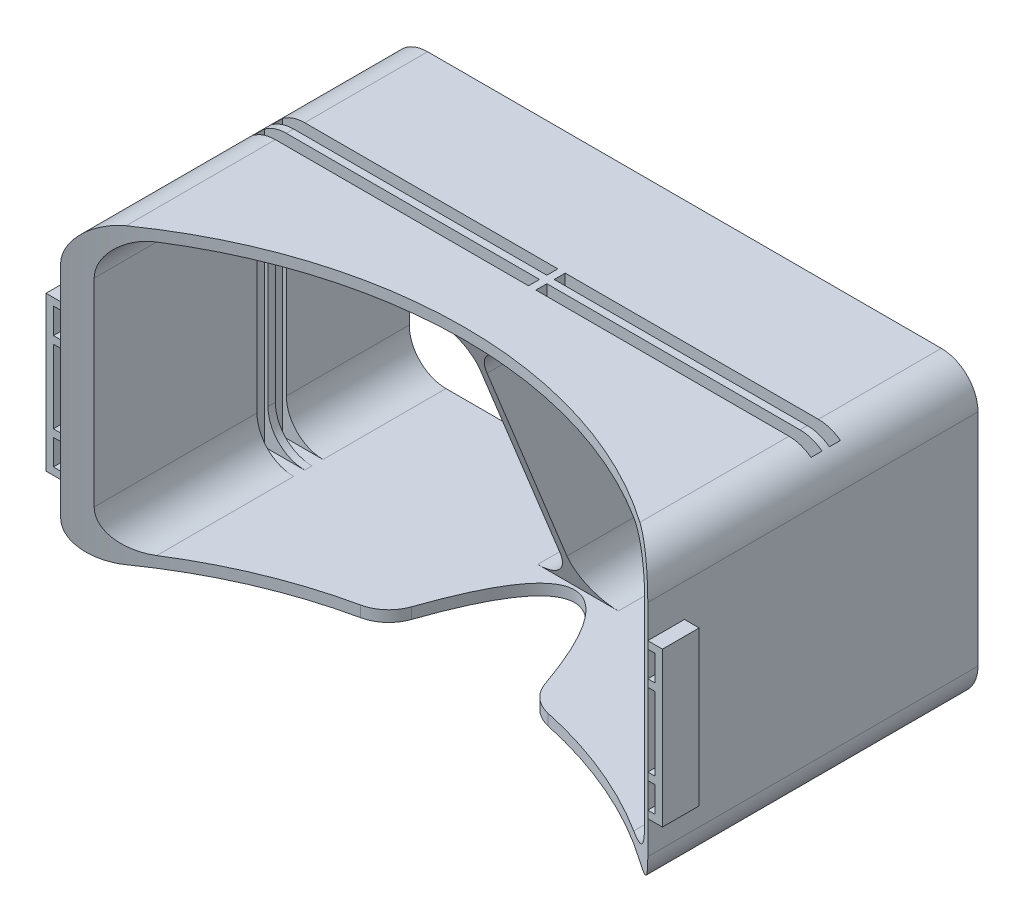
SolidWorks part; units mm, degrees
ref_plane "Plano frontal" through (0, 0, 0) normal (0, 0, 1) x (1, 0, 0)
ref_plane "Plano superior" through (0, 0, 0) normal (0, 1, 0) x (1, 0, 0)
ref_plane "Plano direito" through (0, 0, 0) normal (1, 0, 0) x (0, 0, -1)
sketch "Esboço1" plane through (0, 0, 0) normal (0, 0, 1) x (1, 0, 0)
  line L1 (-86.9655, 43.3333) -> (73.0345, 43.3333)
  line L2 (-86.9655, 43.3333) -> (-86.9655, -36.6667)
  line L3 (-86.9655, -36.6667) -> (73.0345, -36.6667)
  line L4 (73.0345, 43.3333) -> (73.0345, -36.6667)
  dimension "D1" = 160
  dimension "D2" = 80
extrude "Ressalto-extrusão1" add sketch "Esboço1" along normal blind 90
sketch "Esboço2" plane through (0, 0, 90) normal (0, 0, 1) x (1, 0, 0)
  line L0 (-86.9655, 43.3333) -> (-86.9655, -36.6667) construction
  line L1 (-81.9655, 40.3333) -> (68.0345, 40.3333)
  line L2 (-81.9655, 40.3333) -> (-81.9655, -33.6667)
  line L3 (-81.9655, -33.6667) -> (68.0345, -33.6667)
  line L4 (68.0345, 40.3333) -> (68.0345, -33.6667)
  line L5 (73.0345, -36.6667) -> (73.0345, 43.3333) construction
  line L6 (-86.9655, -36.6667) -> (73.0345, -36.6667) construction
  dimension "D1" = 3
  dimension "D2" = 5
  dimension "D3" = 5
  dimension "D4" = 3
extrude "Corte-extrusão1" cut sketch "Esboço2" against normal blind 90
sketch "Esboço3" plane through (0, 43.3333, 0) normal (0, 1, 0) x (1, 0, 0)
  line L0 (-86.9655, -90) -> (73.0345, -90)
  line L1 (-6.9655, -90) -> (-6.9655, -60)
  arc A0 (-86.9655, -90) -> (73.0345, -90) centre (-6.9655, -181.6667) cw
  line M3 (-86.9655, -90) -> (73.0345, -90)
  dimension "D1" = 30
extrude "Corte-extrusão2" cut sketch "Esboço3" against normal blind 90 contours A0 L1 L0 | A0 L1 M3
sketch "Esboço4" plane through (0, -36.6667, 0) normal (0, -1, 0) x (1, 0, 0)
  line L0 (-86.9655, 30) -> (73.0345, 30)
  line L1 (-86.9655, 90) -> (-86.9655, 0) construction
  line L2 (73.0345, 90) -> (73.0345, 0) construction
  line L3 (-6.9655, 60) -> (-86.9655, 60)
  line L4 (-6.9655, 60) -> (-6.9655, 30)
  line L5 (-26.9655, 61.6551) -> (-26.9655, 30)
  line L6 (13.0345, 61.6551) -> (13.0345, 30)
  arc A0 (-86.9655, 90) -> (73.0345, 90) centre (-6.9655, 181.6667) ccw construction
  dimension "D1" = 60
  dimension "D2" = 60
  dimension "D3" = 60
  dimension "D4" = 60
sketch "Esboço5" plane through (0, -36.6667, 0) normal (0, -1, 0) x (1, 0, 0)
  spline S0 degree 2 poles (-26.9655, 61.6551) (-6.9655, -1.6551) (13.0345, 61.6551) knots 0 0 0 1 1 1
extrude "Corte-extrusão3" cut sketch "Esboço5" along normal through all from surface at -3
fillet "Filete1" radius 10 2 edges at (-26.9655, -35.1667, 61.6551)
fillet "Filete2" radius 10 2 edges at (13.0345, -35.1667, 61.6551)
ref_plane "Plano1" through (-5.9655, 0, 0) normal (-1, 0, 0) x (0, 0, 1)
sketch "Esboço7" plane through (-5.9655, 0, 0) normal (-1, 0, 0) x (0, 0, 1)
  line L0 (60, 43.3333) -> (0, 43.3333)
  line L1 (90, 43.3333) -> (0, 43.3333) construction
  line L2 (60, 43.3333) -> (28, -36.6667)
  line L3 (90, -36.6667) -> (0, -36.6667) construction
  line L4 (28, -36.6667) -> (0, -36.6667)
  line L5 (0, -36.6667) -> (0, 43.3333)
  dimension "D1" = 30
  dimension "D2" = 28
extrude "Ressalto-extrusão3" add sketch "Esboço7" along normal blind 2
sketch "Esboço8" plane through (0, 43.3333, 0) normal (0, 1, 0) x (1, 0, 0)
  line L1 (-82.9655, -33.5) -> (-7.9655, -33.5)
  line L2 (-82.9655, -33.5) -> (-82.9655, -36.5)
  line L3 (-82.9655, -36.5) -> (-7.9655, -36.5)
  line L4 (-7.9655, -33.5) -> (-7.9655, -36.5)
  line L6 (73.0345, -90) -> (73.0345, 0) construction
  line L7 (-5.9655, -33.5) -> (69.0345, -33.5)
  line L8 (-5.9655, -33.5) -> (-5.9655, -36.5)
  line L9 (-5.9655, -36.5) -> (69.0345, -36.5)
  line L10 (69.0345, -33.5) -> (69.0345, -36.5)
  line L11 (-82.9655, -38.5) -> (-7.9655, -38.5)
  line L12 (-82.9655, -38.5) -> (-82.9655, -41.5)
  line L13 (-82.9655, -41.5) -> (-7.9655, -41.5)
  line L14 (-7.9655, -38.5) -> (-7.9655, -41.5)
  line L15 (-5.9655, -38.5) -> (69.0345, -38.5)
  line L16 (-5.9655, -38.5) -> (-5.9655, -41.5)
  line L17 (-5.9655, -41.5) -> (69.0345, -41.5)
  line L18 (69.0345, -38.5) -> (69.0345, -41.5)
  dimension "D1" = 3
  dimension "D2" = 75
  dimension "D3" = 4
  dimension "D4" = 4
  dimension "D5" = 75
  dimension "D6" = 53.5
  dimension "D7" = 53.5
  dimension "D8" = 3
  dimension "D9" = 75
  dimension "D10" = 75
  dimension "D11" = 4
  dimension "D12" = 4
  dimension "D13" = 2
  dimension "D14" = 2
  dimension "D15" = 3
  dimension "D16" = 3
sketch "Esboço9" plane through (-86.9655, 0, 0) normal (-1, 0, 0) x (0, 0, 1)
  line L0 (90, 43.3333) -> (90, -36.6667) construction
  line L1 (90, 24.3333) -> (80, 24.3333)
  line L2 (90, 24.3333) -> (90, -17.6667)
  line L3 (90, -17.6667) -> (80, -17.6667)
  line L4 (80, 24.3333) -> (80, -17.6667)
  dimension "D1" = 19
  dimension "D2" = 42
  dimension "D3" = 10
sketch "Esboço14" plane through (-5.9655, 0, 0) normal (-1, 0, 0) x (0, 0, 1)
  line L0 (0, 43.3333) -> (0, -36.6667) construction
  line L1 (0, -3.6667) -> (40, -3.6667)
  line L2 (0, -3.6667) -> (0, -33.6667)
  line L3 (0, -33.6667) -> (40, -33.6667)
  line L4 (40, -3.6667) -> (40, -33.6667)
  line L5 (90, -36.6667) -> (0, -36.6667) construction
  dimension "D1" = 40
  dimension "D2" = 30
  dimension "D3" = 3
extrude "Ressalto-extrusão10" add sketch "Esboço14" along normal blind 2
fillet "Filete15" radius 10 3 edges at (-5.9655, -33.6667, 35.0396) (-5.9655, -33.6667, 15.0396)
fillet "Filete16" radius 10 2 edges at (-7.9655, -33.6667, 35.0396) (-7.9655, -33.6667, 15.0396)
sketch "Esboço16" plane through (-5.9655, 0, 0) normal (-1, 0, 0) x (0, 0, 1)
  line L0 (29, -33.6667) -> (58.8, 40.3333)
  line L1 (58.8, 40.3333) -> (60, -33.6667)
  line L2 (60, -33.6667) -> (29, -33.6667)
  line L3 (90, -36.6667) -> (0, -36.6667) construction
  line L4 (90, 43.3333) -> (0, 43.3333) construction
  dimension "D1" = 3
  dimension "D2" = 3
  dimension "D3" = 3
  dimension "D4" = 29
  dimension "D5" = 30
  dimension "D6" = 31.2
extrude "Corte-extrusão8" cut sketch "Esboço16" against normal blind 20 and the other way blind 20
fillet "Filete17" radius 10 1 edges at (-81.9655, 40.3333, 42.933)
fillet "Filete18" radius 10 1 edges at (-5.9655, 40.3333, 29.4)
fillet "Filete19" radius 10 1 edges at (68.0345, 40.3333, 42.933)
fillet "Filete20" radius 10 1 edges at (-7.9655, 40.3333, 29.4)
fillet "Filete21" radius 10 1 edges at (68.0345, -33.6667, 42.933)
fillet "Filete22" radius 10 1 edges at (-81.9655, -33.6667, 42.933)
extrude "Corte-extrusão9" cut sketch "Esboço8" against normal blind 77
fillet "Filete24" radius 10 1 edges at (73.0345, -36.6667, 45)
fillet "Filete25" radius 10 1 edges at (-86.9655, -36.6667, 45)
fillet "Filete26" radius 10 3 edges at (-82.9655, 43.3333, 35) (-82.9655, 43.3333, 40) (-86.9655, 43.3333, 45)
fillet "Filete27" radius 10 3 edges at (69.0345, 43.3333, 35) (69.0345, 43.3333, 40) (73.0345, 43.3333, 45)
extrude "Ressalto-extrusão11" add sketch "Esboço9" along normal blind 4
sketch "Esboço17" plane through (0, 0, 90) normal (0, 0, 1) x (1, 0, 0)
  line L0 (-86.9655, -17.6667) -> (-86.9655, 24.3333) construction
  line L1 (-88.9655, 22.3333) -> (-86.9655, 22.3333)
  line L2 (-88.9655, 22.3333) -> (-88.9655, 15.3333)
  line L3 (-88.9655, 15.3333) -> (-86.9655, 15.3333)
  line L4 (-86.9655, 22.3333) -> (-86.9655, 15.3333)
  line L5 (-88.9655, 13.3333) -> (-86.9655, 13.3333)
  line L6 (-88.9655, 13.3333) -> (-88.9655, -6.6667)
  line L7 (-88.9655, -6.6667) -> (-86.9655, -6.6667)
  line L8 (-86.9655, 13.3333) -> (-86.9655, -6.6667)
  line L9 (-88.9655, -8.6667) -> (-86.9655, -8.6667)
  line L10 (-88.9655, -8.6667) -> (-88.9655, -15.6667)
  line L11 (-88.9655, -15.6667) -> (-86.9655, -15.6667)
  line L12 (-86.9655, -8.6667) -> (-86.9655, -15.6667)
  line L13 (-90.9655, 24.3333) -> (-86.9655, 24.3333) construction
  line L14 (-90.9655, -17.6667) -> (-86.9655, -17.6667) construction
  dimension "D1" = 0
  dimension "D2" = 0
  dimension "D3" = 0
  dimension "D4" = 2
  dimension "D5" = 2
  dimension "D6" = 2
  dimension "D7" = 2
  dimension "D8" = 11
  dimension "D9" = 7
  dimension "D10" = 20
  dimension "D11" = 2
  dimension "D12" = 7
extrude "Corte-extrusão10" cut sketch "Esboço17" against normal blind 10
sketch "Esboço18" plane through (73.0345, 0, 0) normal (1, 0, 0) x (0, 0, -1)
  line L0 (-90, -26.6667) -> (-90, 33.3333) construction
  line L1 (-90, 24.3333) -> (-80, 24.3333)
  line L2 (-90, 24.3333) -> (-90, -17.6667)
  line L3 (-90, -17.6667) -> (-80, -17.6667)
  line L4 (-80, 24.3333) -> (-80, -17.6667)
  line L5 (-82.154, 43.3333) -> (-41.5, 43.3333) construction
  dimension "D1" = 19
  dimension "D2" = 42
  dimension "D3" = 10
extrude "Ressalto-extrusão12" add sketch "Esboço18" along normal blind 4
sketch "Esboço19" plane through (0, 0, 90) normal (0, 0, 1) x (1, 0, 0)
  line L0 (73.0345, 24.3333) -> (73.0345, -17.6667) construction
  line L1 (73.0345, 22.3333) -> (75.0345, 22.3333)
  line L2 (73.0345, 22.3333) -> (73.0345, 15.3333)
  line L3 (73.0345, 15.3333) -> (75.0345, 15.3333)
  line L4 (75.0345, 22.3333) -> (75.0345, 15.3333)
  line L5 (73.0345, 13.3333) -> (75.0345, 13.3333)
  line L6 (73.0345, 13.3333) -> (73.0345, -6.6667)
  line L7 (73.0345, -6.6667) -> (75.0345, -6.6667)
  line L8 (75.0345, 13.3333) -> (75.0345, -6.6667)
  line L9 (73.0345, -8.6667) -> (75.0345, -8.6667)
  line L10 (73.0345, -8.6667) -> (73.0345, -15.6667)
  line L11 (73.0345, -15.6667) -> (75.0345, -15.6667)
  line L12 (75.0345, -8.6667) -> (75.0345, -15.6667)
  line L13 (77.0345, 24.3333) -> (73.0345, 24.3333) construction
  line L14 (77.0345, -17.6667) -> (73.0345, -17.6667) construction
  dimension "D1" = 0
  dimension "D2" = 0
  dimension "D3" = 0
  dimension "D4" = 2
  dimension "D5" = 2
  dimension "D6" = 2
  dimension "D7" = 2
  dimension "D8" = 11
  dimension "D9" = 7
  dimension "D10" = 20
  dimension "D11" = 2
  dimension "D12" = 7
extrude "Corte-extrusão11" cut sketch "Esboço19" against normal blind 10
